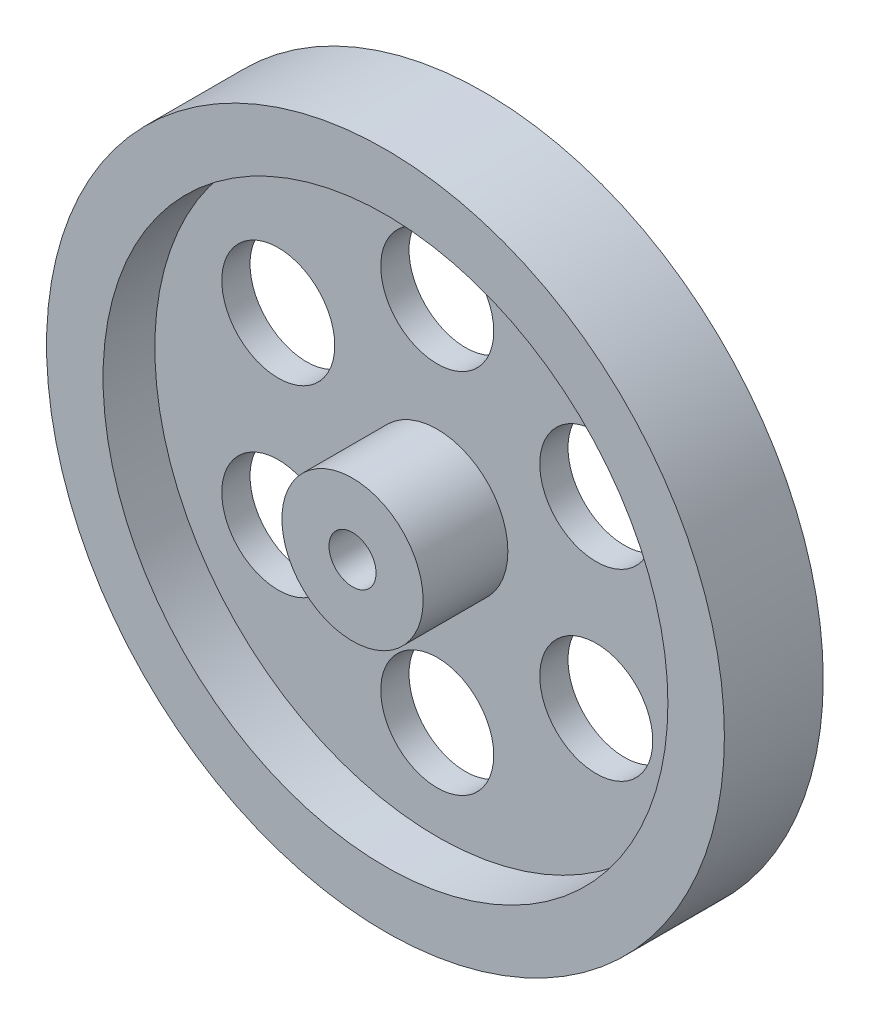
SolidWorks part; units mm, degrees
ref_plane "Plan de face" through (0, 0, 0) normal (0, 0, 1) x (1, 0, 0)
ref_plane "Plan de dessus" through (0, 0, 0) normal (0, 1, 0) x (1, 0, 0)
ref_plane "Plan de droite" through (0, 0, 0) normal (1, 0, 0) x (0, 0, -1)
sketch "Esquisse1" plane through (0, 0, 0) normal (0, 0, 1) x (1, 0, 0)
  line L0 (0, 0) -> (0, 36) construction
  circle A0 centre (0, 0) radius 2.5
  circle A1 centre (0, 0) radius 36
  circle A2 centre (0, 0) radius 7.5
  circle A3 centre (0, 0) radius 30
  circle A4 centre (0, 19.5) radius 6
  circle A5 centre (16.8875, 9.75) radius 6
  circle A6 centre (16.8875, -9.75) radius 6
  circle A7 centre (0, -19.5) radius 6
  circle A8 centre (-16.8875, -9.75) radius 6
  circle A9 centre (-16.8875, 9.75) radius 6
  point P22 (0, 0)
  dimension "D1" = 72
  dimension "D2" = 5
  dimension "D3" = 15
  dimension "D4" = 60
  dimension "D6" = 12
  dimension "D5" = 19.5
  dimension "D7" = 6
extrude "Boss.-Extru.1" add sketch "Esquisse1" along normal blind 12 contours A0 A2 region at (-7.2879, 0, 0)
extrude "Boss.-Extru.2" add sketch "Esquisse1<3>" along normal blind 3 contours A2 A4 A3 A9 A8 A7 A6 A5 region at (-29.1515, 0, 0)
sketch "Esquisse1<3>" plane through (0, 0, 0) normal (0, 0, 1) x (1, 0, 0) same geometry as "Esquisse1"
extrude "Boss.-Extru.3" add sketch "Esquisse1<4>" along normal blind 8.5 and the other way blind 2 contours A3 A1 region at (-34.9818, 0, 0)
sketch "Esquisse1<4>" plane through (0, 0, 0) normal (0, 0, 1) x (1, 0, 0) same geometry as "Esquisse1"
